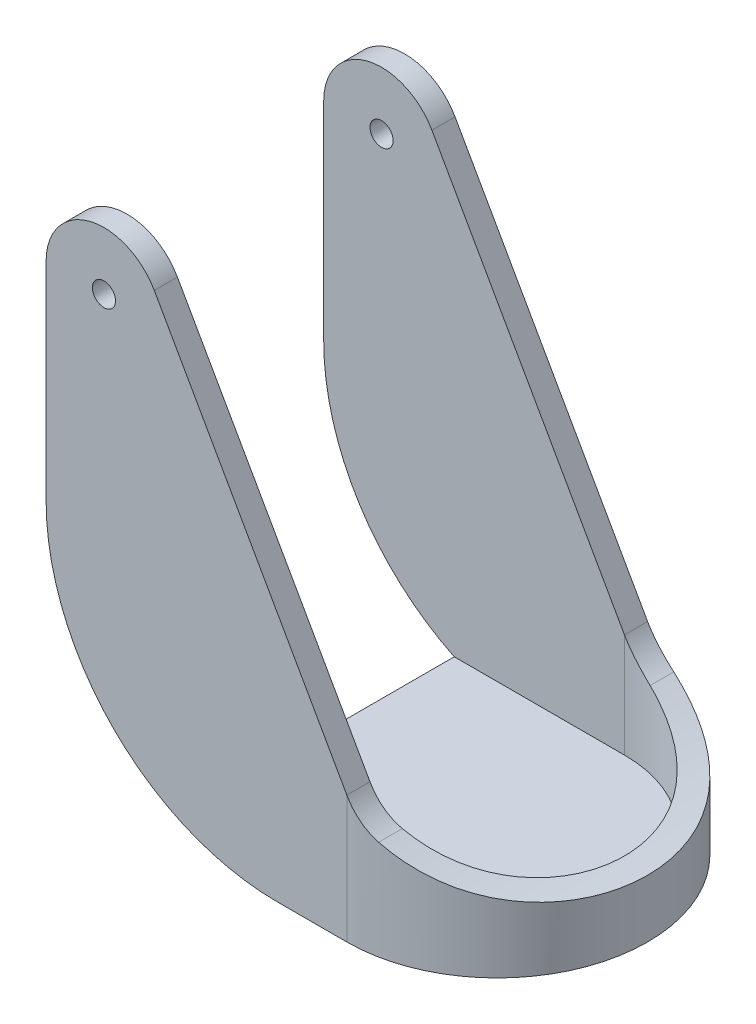
SolidWorks part; units mm, degrees
ref_plane "前视基准面" through (0, 0, 0) normal (0, 0, 1) x (1, 0, 0)
ref_plane "上视基准面" through (0, 0, 0) normal (0, 1, 0) x (1, 0, 0)
ref_plane "右视基准面" through (0, 0, 0) normal (1, 0, 0) x (0, 0, -1)
sketch "草图1" plane through (0, 0, 0) normal (0, 1, 0) x (1, 0, 0)
  line L1 (-24, -22.5) -> (24, -22.5)
  line L2 (-28, -18.5) -> (-28, 18.5)
  line L3 (-24, 22.5) -> (24, 22.5)
  line L4 (28, -18.5) -> (28, 18.5)
  line L5 (-28, -22.5) -> (28, 22.5) construction
  line L6 (-28, 22.5) -> (28, -22.5) construction
  line L7 (-23, 17.5) -> (23, 17.5)
  line L8 (-23, 17.5) -> (-23, -17.5)
  line L9 (-23, -17.5) -> (23, -17.5)
  line L10 (23, 17.5) -> (23, -17.5)
  line L11 (-23, 17.5) -> (23, -17.5) construction
  line L12 (-23, -17.5) -> (23, 17.5) construction
  circle A0 centre (-23, 17.5) radius 2.15
  circle A1 centre (-23, -17.5) radius 2.15
  circle A2 centre (23, -17.5) radius 2.15
  circle A3 centre (23, 17.5) radius 2.15
  arc A4 (-28, 18.5) -> (-24, 22.5) centre (-24, 18.5) cw
  arc A5 (-24, -22.5) -> (-28, -18.5) centre (-24, -18.5) cw
  arc A6 (24, -22.5) -> (28, -18.5) centre (24, -18.5) ccw
  arc A7 (24, 22.5) -> (28, 18.5) centre (24, 18.5) cw
  point P0 (0, 0)
  point P6 (0, 0)
  dimension "D3" = 4.3
  dimension "D4" = 4.3
  dimension "D5" = 4.3
  dimension "D6" = 4.3
  dimension "D9" = 4
  dimension "D1" = 46
  dimension "D2" = 35
  dimension "D7" = 56
  dimension "D8" = 45
extrude "凸台-拉伸1" add sketch "草图1" along normal blind 1 contours A7 L3 A4 L2 A5 L1 A6 L4 A3 L10 A2 L9 A1 L8 A0 L7 | A3 L7 A0 L8 A1 L9 A2 L10 region at (-26.3204, 0, 20.8204) region at (0, 0, 0)
sketch "草图3" plane through (0, 1, 0) normal (0, 1, 0) x (1, 0, 0)
  line L0 (-27.7654, 0) -> (31.8476, 0) construction
  line L1 (-26, -13) -> (-26, 13)
  line L2 (-26, 13) -> (0, 13)
  line L3 (-26, -13) -> (0, -13)
  arc A0 (0, -13) -> (0, 13) centre (0, 0) ccw
  point P10 (-12.768, 0)
  point P11 (-26, 0)
  dimension "D1" = 26
  dimension "D2" = 26
  dimension "D3" = 26
extrude "凸台-拉伸2" add sketch "草图3" along normal blind 12
sketch "草图8" plane through (0, 0, 13) normal (0, 0, 1) x (1, 0, 0)
  line L0 (-26, 13) -> (-26, 40)
  line L1 (-26, 13) -> (-26, 1) construction
  line L2 (-26, 13) -> (0, 13) construction
  line L3 (-16.6469, 42.4598) -> (0, 13)
  line L4 (-24, 0) -> (24, 0) construction
  line L5 (-26, 13) -> (0, 13)
  arc A0 (-26, 40) -> (-16.6469, 42.4598) centre (-21, 40) cw
  circle A1 centre (-21, 40) radius 1
  dimension "D2" = 5
  dimension "D3" = 2
  dimension "D1" = 40
extrude "凸台-拉伸4" add sketch "草图8" against normal blind 2
mirror "镜向1" about plane through (0, 0, 0) normal (0, 0, 1) of "凸台-拉伸4"
sketch "草图9" plane through (0, 13, 0) normal (0, 1, 0) x (1, 0, 0)
  line L0 (0, 0) -> (-22.8565, 0) construction
  line L1 (-26, 11) -> (-26, -11) construction
  line L2 (-26, 11) -> (-26, -11)
  line L3 (-26, 11) -> (0, 11)
  line L4 (-26, -11) -> (0, -11)
  arc A0 (0, -11) -> (0, 11) centre (0, 0) ccw
  arc A1 (0, -13) -> (0, 13) centre (0, 0) ccw construction
  point P9 (-10.08, 0)
  dimension "D1" = 2
extrude "切除-拉伸1" cut sketch "草图9" against normal offset from surface (9 mm away) 3 up to face at (-23, 1, -15.35)
sketch "草图11" plane through (0, 0, 0) normal (0, 0, 1) x (1, 0, 0)
  line L0 (0, 13) -> (0, 1) construction
  line L1 (0, 13) -> (0, 1) construction
  line L2 (0, 1) -> (13, 1) construction
  line L3 (13, 1) -> (13, 7) construction
  line L4 (13, 1) -> (13, 13) construction
  line L7 (0, 13) -> (-16.6469, 42.4598) construction
  line L8 (0, 13) -> (13, 13)
  line L9 (13, 13) -> (13, 7)
  arc A0 (0, 13) -> (2.5075, 10.6018) centre (5.2237, 15.9518) ccw
  arc A1 (2.5075, 10.6018) -> (13, 7) centre (20.6153, 46.2684) ccw
  dimension "D1" = 6
  dimension "D3" = 40
  dimension "D2" = 6
extrude "切除-拉伸2" cut sketch "草图11" against normal mid plane 40
sketch "草图12" plane through (0, 1, 0) normal (0, 1, 0) x (1, 0, 0)
  line L0 (-26, -13) -> (0, -13) construction
  line L1 (-26, -13) -> (0, -13)
  line L2 (-26, 13) -> (-26, -13) construction
  line L3 (-26, 13) -> (-26, -13)
  line L4 (0, 13) -> (-26, 13) construction
  line L5 (0, 13) -> (-26, 13)
  arc A0 (0, -13) -> (0, 13) centre (0, 0) ccw construction
  arc A1 (0, -13) -> (0, 13) centre (0, 0) ccw
  circle A2 centre (0, 0) radius 3
  dimension "D1" = 6
extrude "切除-拉伸3" cut sketch "草图12" along normal blind 1
fillet "圆角1" radius 20 1 edges at (-26, 2, 0)
sketch "草图13" plane through (0, 0, 0) normal (0, -1, 0) x (1, 0, 0)
  line L1 (-30, -25) -> (30, -25)
  line L2 (-30, -25) -> (-30, 25)
  line L3 (-30, 25) -> (30, 25)
  line L4 (30, -25) -> (30, 25)
  line L5 (-30, -25) -> (30, 25) construction
  line L6 (-30, 25) -> (30, -25) construction
  point P0 (0, 0)
  dimension "D1" = 60
  dimension "D2" = 50
extrude "切除-拉伸4" cut sketch "草图13" against normal up to surface (1 mm away) up to face at (-23, 1, -15.35)
sketch3d "URDF Reference"
  line L0 (0, 0, 0) -> (10, 0, 0) construction
  line L1 (0, 0, 0) -> (0, 0, -10) construction
  point P0 (0, 0, 0)
